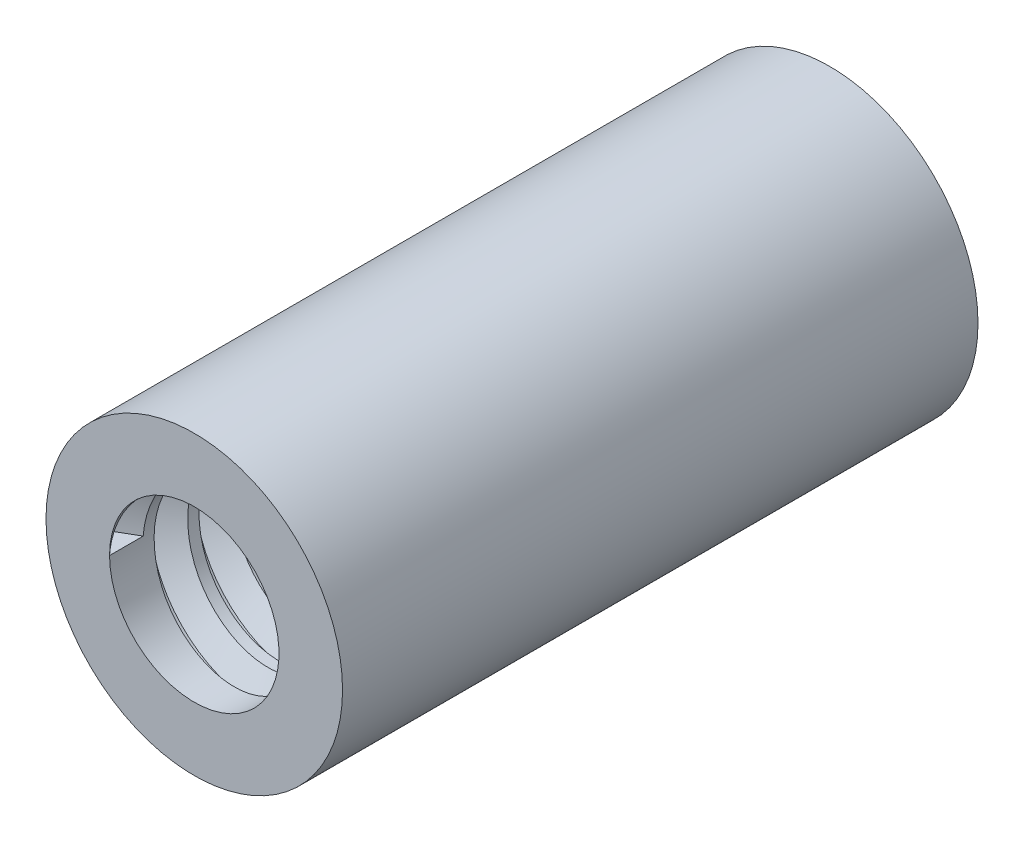
SolidWorks part; units mm, degrees
ref_plane "Front Plane" through (0, 0, 0) normal (0, 0, 1) x (1, 0, 0)
ref_plane "Top Plane" through (0, 0, 0) normal (0, 1, 0) x (1, 0, 0)
ref_plane "Right Plane" through (0, 0, 0) normal (1, 0, 0) x (0, 0, -1)
sketch "Sketch1" plane through (0, 0, 0) normal (0, 0, 1) x (1, 0, 0)
  circle A0 centre (0, 0) radius 3.5
  dimension "D1" = 7
extrude "Boss-Extrude1" add sketch "Sketch1" along normal blind 15
sketch "Sketch2" plane through (0, 0, 15) normal (0, 0, 1) x (1, 0, 0)
  circle A0 centre (0, 0) radius 2
  point P3 (0, 0)
  dimension "D1" = 4
extrude "Cut-Extrude1" cut sketch "Sketch2" against normal blind 7
thread "Thread1" pitch 1.0583 method cut profile "Thread Profile1" start angle 0, offset 0, length 12, pitch 1.0583, diameter 4
ref_plane "Plane1" through (-2, 0, 15) normal (0, -1, 0) x (-1, 0, 0)
sketch "Thread Profile1" plane through (-2, 0, 15) normal (0, -1, 0) x (-1, 0, 0)
  line L0 (0, 0) -> (0, 1.0583) construction
  line L1 (0, 0) -> (0.5728, 0.3307)
  line L2 (0.5728, 0.3307) -> (0.5728, 0.463)
  line L3 (0.5728, 0.463) -> (0, 0.7937)
  line L4 (0.5728, 0.3969) -> (0, 0.3969) construction
  line L11 (0, 0) -> (0, 0.7937)
  point P2 (0, 0)
  dimension "Pitch" = 1.0583
  dimension "Profile_Angle" = 60
  dimension "Profile_Land" = 0.1323
  dimension "Profile_Height" = 0.5728
